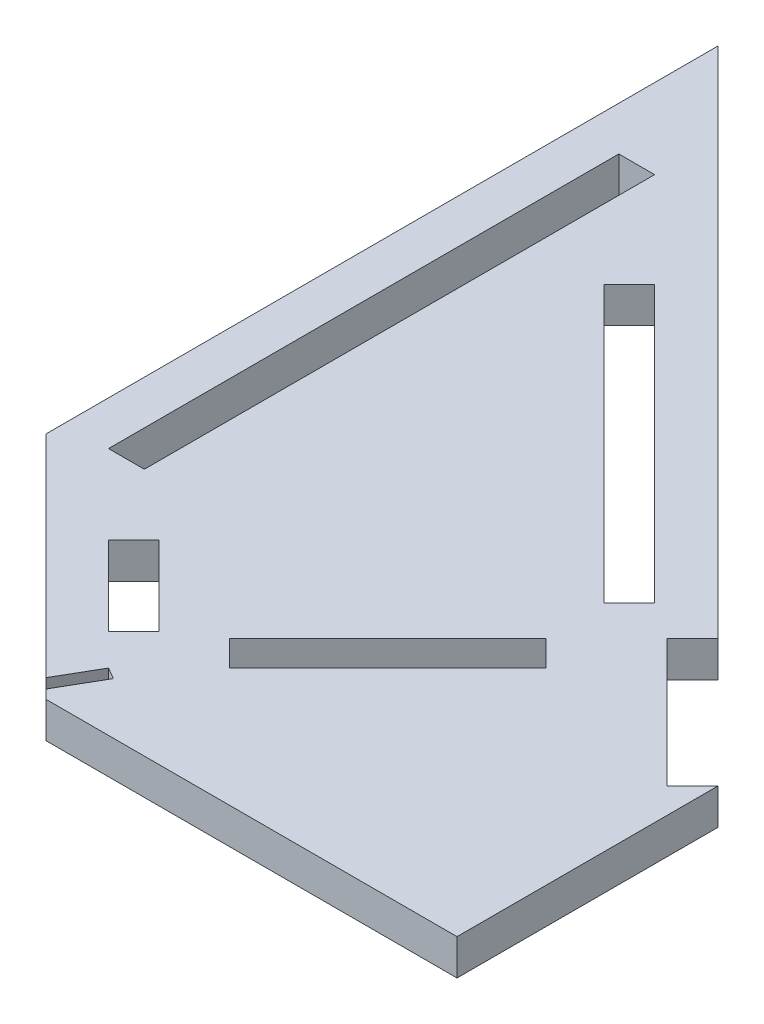
SolidWorks part; units mm, degrees
ref_plane "Front Plane" through (0, 0, 0) normal (0, 0, 1) x (1, 0, 0)
ref_plane "Top Plane" through (0, 0, 0) normal (0, 1, 0) x (1, 0, 0)
ref_plane "Right Plane" through (0, 0, 0) normal (1, 0, 0) x (0, 0, -1)
sketch "Sketch1" plane through (0, 0, 0) normal (0, 1, 0) x (1, 0, 0)
  line L0 (0, 0) -> (0, 58.25)
  line L1 (0, 58.25) -> (-143.0789, 201.3289)
  line L2 (-143.0789, 201.3289) -> (-143.0789, 51.3289)
  line L3 (-143.0789, 51.3289) -> (-95.9462, 4.1962)
  line L4 (-91.75, 0) -> (0, 0)
  line L5 (-93.75, 2) -> (-91.75, 0)
  line L6 (-82.9929, 32.1972) -> (-77.336, 26.5404) construction
  line L7 (-47.6375, 67.5526) -> (-82.9929, 32.1972) construction
  line L8 (-47.6375, 67.5526) -> (-41.9807, 61.8957) construction
  line L9 (-298.2472, -352.1996) -> (-88.2472, 11.5311)
  line L10 (-88.2472, 11.5311) -> (-90.8453, 13.0311)
  line L11 (-90.8453, 13.0311) -> (-300.8453, -350.6996)
  line L12 (-300.8453, -350.6996) -> (-298.2472, -352.1996)
  line L13 (-93.75, 2) -> (-88.2472, 11.5311)
  line L14 (-88.2472, 11.5311) -> (-90.8453, 13.0311)
  line L15 (-90.8453, 13.0311) -> (-95.9462, 4.1962)
  line L17 (-41.9807, 61.8957) -> (-77.336, 26.5404) construction
  line L18 (-109.7154, 142.5174) -> (-48.0839, 80.886)
  line L19 (-48.0839, 80.886) -> (-42.4271, 86.5429)
  line L20 (-42.4271, 86.5429) -> (-104.0585, 148.1743)
  line L21 (-104.0585, 148.1743) -> (-109.7154, 142.5174)
  line L22 (-109.7154, 142.5174) -> (-48.0839, 80.886)
  line L23 (-48.0839, 80.886) -> (-42.4271, 86.5429)
  line L24 (-42.4271, 86.5429) -> (-104.0585, 148.1743)
  line L25 (-104.0585, 148.1743) -> (-109.7154, 142.5174)
  line L34 (-125.2717, 55.4575) -> (-125.2717, 169.3875)
  line L35 (-125.2717, 169.3875) -> (-133.2717, 169.3875)
  line L36 (-133.2717, 169.3875) -> (-133.2717, 55.4575)
  line L37 (-133.2717, 55.4575) -> (-125.2717, 55.4575)
  line L38 (-125.2717, 55.4575) -> (-125.2717, 169.3875)
  line L39 (-125.2717, 169.3875) -> (-133.2717, 169.3875)
  line L40 (-133.2717, 169.3875) -> (-133.2717, 55.4575)
  line L41 (-133.2717, 55.4575) -> (-125.2717, 55.4575)
  line L42 (-82.9929, 32.1972) -> (-77.336, 26.5404)
  line L43 (-47.6375, 67.5526) -> (-82.9929, 32.1972)
  line L44 (-47.6375, 67.5526) -> (-41.9807, 61.8957)
  line L45 (-41.9807, 61.8957) -> (-77.336, 26.5404)
  line L47 (-115.594, 37.7798) -> (-97.9164, 20.1022)
  line L50 (-97.9164, 20.1022) -> (-92.2595, 25.759)
  line L52 (-92.2595, 25.759) -> (-109.9372, 43.4367)
  line L54 (-109.9372, 43.4367) -> (-115.594, 37.7798)
  line L55 (-34.1283, 81.0618) -> (-5.6601, 52.5937)
  line L56 (-5.6601, 52.5937) -> (-0.0033, 58.2506)
  line L57 (-0.0033, 58.2506) -> (-28.4714, 86.7187)
  line L58 (-28.4714, 86.7187) -> (-34.1283, 81.0618)
  line L59 (-34.1283, 81.0618) -> (-5.6601, 52.5937)
  line L60 (-5.6601, 52.5937) -> (-0.0033, 58.2506)
  line L61 (-0.0033, 58.2506) -> (-28.4714, 86.7187)
  line L62 (-28.4714, 86.7187) -> (-34.1283, 81.0618)
  line L63 (-115.594, 37.7798) -> (-97.9164, 20.1022)
  line L64 (-97.9164, 20.1022) -> (-92.2595, 25.759)
  line L65 (-92.2595, 25.759) -> (-109.9372, 43.4367)
  line L66 (-109.9372, 43.4367) -> (-115.594, 37.7798)
  dimension "D1" = 135
  dimension "D2" = 150
  dimension "D3" = 72.59
  dimension "D4" = 91.75
  dimension "D5" = 0
  dimension "D6" = 0
  dimension "D7" = 0
  dimension "D8" = 0
  dimension "D9" = 0
extrude "Boss-Extrude1" add sketch "Sketch1" along normal blind 8 contours L62 L1 L2 L3 L15 L14 L13 L5 L4 L0 L59 L41 L40 L39 L38 L25 L24 L23 L22 L44 L45 L42 L43 region at (-80.4323, 0, -73.1393)
